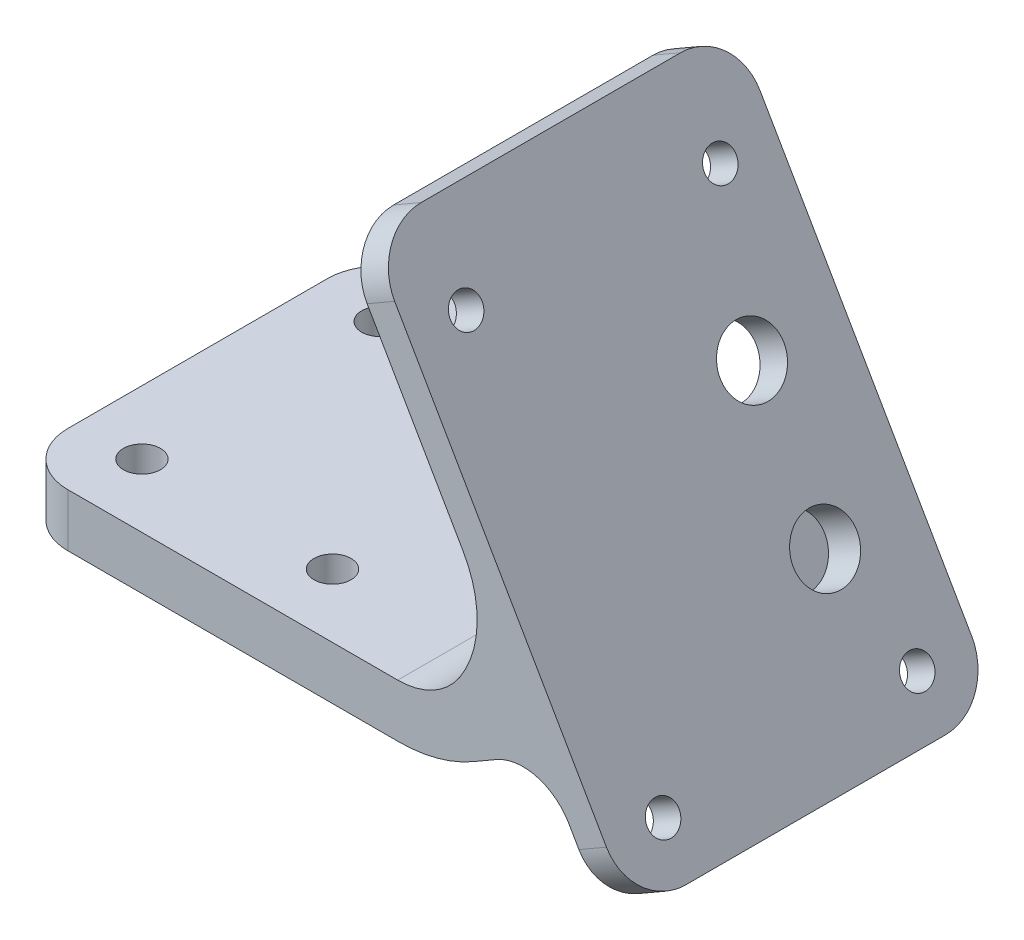
SolidWorks part; units mm, degrees
material "PET"
ref_plane "Přední rovina" through (0, 0, 0) normal (0, 0, 1) x (1, 0, 0)
ref_plane "Horní rovina" through (0, 0, 0) normal (0, 1, 0) x (1, 0, 0)
ref_plane "Pravá rovina" through (0, 0, 0) normal (1, 0, 0) x (0, 0, -1)
sketch "Skica1" plane through (0, 0, 0) normal (0, 0, 1) x (1, 0, 0)
  line L0 (0, 0) -> (38.6603, 0)
  line L1 (56.5705, -11.0215) -> (49.8205, 0.6699)
  line L2 (31.5705, 32.2798) -> (34.1686, 33.7798)
  line L3 (34.1686, 33.7798) -> (59.1686, -9.5215)
  line L4 (59.1686, -9.5215) -> (56.5705, -11.0215)
  line L6 (40, -5) -> (0, -5)
  line L7 (0, -5) -> (0, 0)
  line L8 (40, -5) -> (49.8205, 0.6699)
  line L9 (38.6603, 0) -> (47.3205, 5)
  line L10 (47.3205, 5) -> (31.5705, 32.2798)
  dimension "D1" = 5
  dimension "D2" = 3
  dimension "D3" = 50
  dimension "D4" = 13.5
  dimension "D5" = 40
  dimension "D6" = 60
  dimension "D7" = 5
  dimension "D8" = 90
  dimension "D9" = 10
extrude "Přidat vysunutím1" add sketch "Skica1" along normal blind 34.5
sketch "Skica2" plane through (40.2535, 23.2404, 0) normal (0.866, 0.5, 0) x (0, 0, -1)
  line L0 (-29.25, 5.7699) -> (-29.25, -31.4301) construction
  line L1 (-34.5, 12.1699) -> (0, 12.1699) construction
  line L2 (-34.5, -37.8301) -> (-34.5, 12.1699) construction
  line L3 (-29.25, 5.7699) -> (-5.25, 5.7699) construction
  line L4 (-5.25, 5.7699) -> (-5.25, -31.4301) construction
  line L5 (-5.25, -31.4301) -> (-29.25, -31.4301) construction
  circle A0 centre (-29.25, 5.7699) radius 1.5
  circle A1 centre (-29.25, -31.4301) radius 1.5
  circle A2 centre (-5.25, 5.7699) radius 1.5
  circle A3 centre (-5.25, -31.4301) radius 1.5
  dimension "D1" = 3
  dimension "D2" = 3
  dimension "D6" = 3
  dimension "D7" = 3
  dimension "D3" = 37.2
  dimension "D4" = 6.4
  dimension "D5" = 5.25
  dimension "D8" = 24
extrude "Odebrat vysunutím1" cut sketch "Skica2" against normal up to surface (3 mm away) up to face at (53.1955, -5.1758, 17.25)
sketch "Skica4" plane through (0, 0, 0) normal (0, 1, 0) x (1, 0, 0)
  line L0 (0, -34.5) -> (0, 0) construction
  line L2 (6, -6) -> (24, -6) construction
  line L3 (6, -6) -> (6, -28.5) construction
  line L4 (6, -28.5) -> (24, -28.5) construction
  line L5 (24, -6) -> (24, -28.5) construction
  line L6 (6, -6) -> (24, -28.5) construction
  line L7 (6, -28.5) -> (24, -6) construction
  line L8 (38.6603, 0) -> (0, 0) construction
  line L9 (38.6603, -34.5) -> (0, -34.5) construction
  circle A2 centre (6, -6) radius 1.75
  circle A3 centre (6, -28.5) radius 1.75
  circle A4 centre (24, -28.5) radius 1.75
  circle A5 centre (24, -6) radius 1.75
  point P4 (15, -17.25)
  dimension "D1" = 3.5
  dimension "D2" = 3.5
  dimension "D3" = 3.5
  dimension "D4" = 3.5
  dimension "D5" = 18
  dimension "D6" = 6
  dimension "D7" = 6
  dimension "D8" = 6
extrude "Odebrat vysunutím2" cut sketch "Skica4" against normal up to surface (5 mm away) up to face at (20, -5, 17.25)
sketch "Skica6" plane through (-6.0849, 10.5394, 0) normal (-0.5, 0.866, 0) x (0.866, 0.5, 0)
  line L4 (46.4808, 0) -> (43.4808, 0)
  line L5 (43.4808, 0) -> (43.4808, -34.5)
  line L6 (43.4808, -34.5) -> (46.4808, -34.5)
  line L7 (46.4808, -34.5) -> (46.4808, 0)
  line L8 (46.4808, 0) -> (43.4808, 0)
  line L9 (43.4808, 0) -> (43.4808, -34.5)
  line L10 (43.4808, -34.5) -> (46.4808, -34.5)
  line L11 (46.4808, -34.5) -> (46.4808, 0)
  dimension "D1" = 0
extrude "Přidat vysunutím3" add sketch "Skica6" along normal blind 1.6
sketch "Skica7" plane through (18.9151, -32.7619, 0) normal (0.5, -0.866, 0) x (0.866, 0.5, 0)
  line L4 (43.4808, 0) -> (46.4808, 0)
  line L5 (46.4808, 0) -> (46.4808, 34.5)
  line L6 (46.4808, 34.5) -> (43.4808, 34.5)
  line L7 (43.4808, 34.5) -> (43.4808, 0)
  line L8 (43.4808, 0) -> (46.4808, 0)
  line L9 (46.4808, 0) -> (46.4808, 34.5)
  line L10 (46.4808, 34.5) -> (43.4808, 34.5)
  line L11 (43.4808, 34.5) -> (43.4808, 0)
  dimension "D1" = 0
extrude "Odebrat vysunutím3" cut sketch "Skica7" against normal blind 1.6
fillet "Zaoblit1" radius 5 4 edges at (32.0695, 34.4154, 34.5) (57.0695, -8.8858, 34.5) (57.0695, -8.8858, 0) (32.0695, 34.4154, 0)
fillet "Zaoblit2" radius 5 2 edges at (0, -2.5, 0) (0, -2.5, 34.5)
fillet "Zaoblit3" radius 10 1 edges at (47.3205, 5, 17.25)
fillet "Zaoblit4" radius 5 1 edges at (49.8205, 0.6699, 17.25)
fillet "Zaoblit5" radius 7 1 edges at (38.6603, 0, 17.25)
fillet "Zaoblit6" radius 14 1 edges at (40, -5, 17.25)
sketch "Skica8" plane through (40.2535, 23.2404, 0) normal (0.866, 0.5, 0) x (0, 0, -1)
  line L0 (-29.5, 13.7699) -> (-5, 13.7699) construction
  line L1 (0, -31.2301) -> (0, 8.7699) construction
  circle A0 centre (-8.7, -7.1301) radius 3
  dimension "D1" = 20.9
  dimension "D3" = 6
  dimension "D2" = 8.7
extrude "Odebrat vysunutím5" cut sketch "Skica8" against normal up to surface (4.4583 mm away) up to face at (42.9051, 8.3696, 17.25)
sketch "Skica9" plane through (40.2535, 23.2404, 0) normal (0.866, 0.5, 0) x (0, 0, -1)
  line L0 (-8.7, -7.1301) -> (-8.7, -20.9301) construction
  circle A0 centre (-8.7, -20.9301) radius 3
  dimension "D1" = 13.8
  dimension "D2" = 6
extrude "Odebrat vysunutím6" cut sketch "Skica9" against normal blind 3.5
